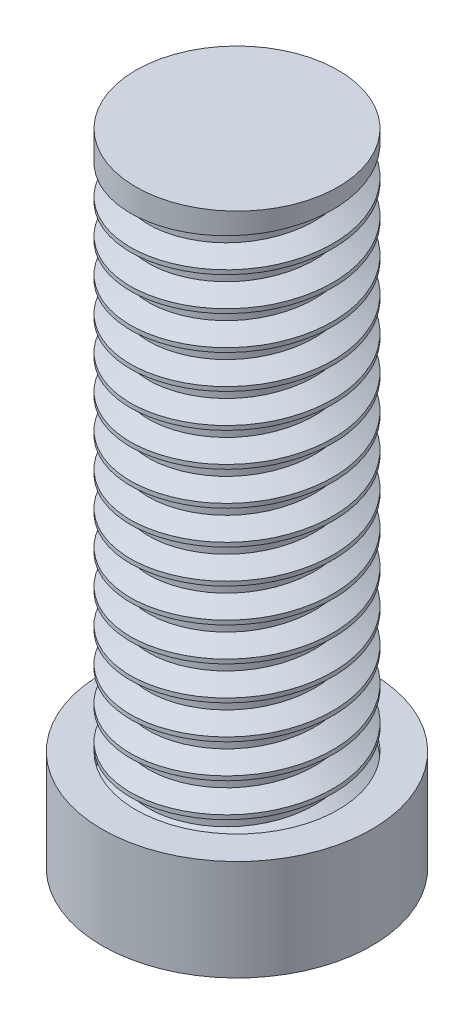
SolidWorks part; units mm, degrees
ref_plane "Front Plane" through (0, 0, 0) normal (0, 0, 1) x (1, 0, 0)
ref_plane "Top Plane" through (0, 0, 0) normal (0, 1, 0) x (1, 0, 0)
ref_plane "Right Plane" through (0, 0, 0) normal (1, 0, 0) x (0, 0, -1)
sketch "Sketch1" plane through (0, 0, 0) normal (0, 1, 0) x (1, 0, 0)
  circle A0 centre (0, 0) radius 2
  dimension "D1" = 4
extrude "Boss-Extrude1" add sketch "Sketch1" along normal blind 1.9
sketch "Sketch2" plane through (0, 1.9, 0) normal (0, 1, 0) x (1, 0, 0)
  circle A0 centre (0, 0) radius 1.5
  dimension "D1" = 3
extrude "Boss-Extrude2" add sketch "Sketch2" along normal blind 8
thread "Thread1" pitch 0.5 method cut profile "Thread Profile1" start angle 0, offset 0, length 0, pitch 0.5, diameter 3
ref_plane "Plane1" through (-1.5, 9.9, 0) normal (0, 0, 1) x (-1, 0, 0)
sketch "Thread Profile1" plane through (-1.5, 9.9, 0) normal (0, 0, 1) x (-1, 0, 0)
  line L0 (0, 0) -> (0, 0.5) construction
  line L11 (0, 0) -> (0, 0.4375)
  line L12 (0, 0.4375) -> (-0.2706, 0.2812)
  line L13 (-0.2706, 0.2812) -> (-0.2706, 0.1562)
  line L15 (-0.2706, 0.1562) -> (0, 0)
  line L17 (-0.2706, 0.2187) -> (0, 0.2187) construction
  point P2 (0, 0)
  dimension "Pitch" = 0.5
  dimension "Profile_Angle" = 60
  dimension "Profile_Land" = 0.125
  dimension "Profile_Height" = 0.2706
chamfer "Chamfer1" distance 0.7 angle 30 1 edges at (0, 0, 2) first distance on face at (0, 0, 2)
